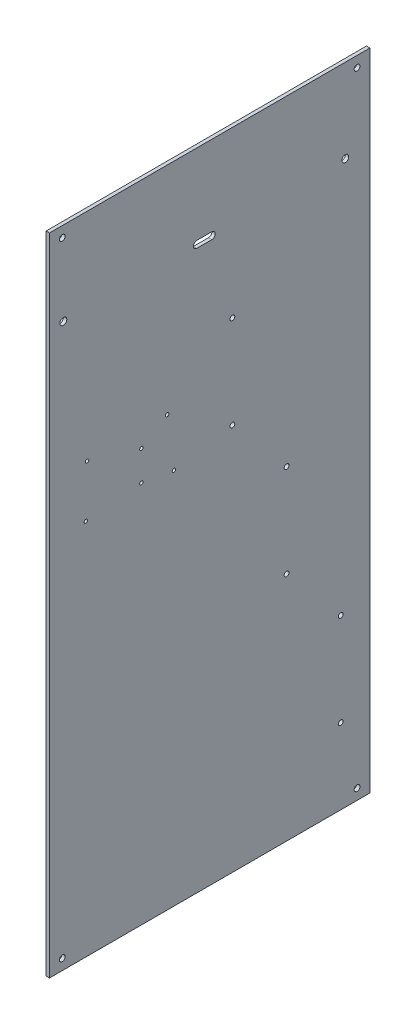
SolidWorks part; units mm, degrees
ref_plane "Front Plane" through (0, 0, 0) normal (0, 0, 1) x (1, 0, 0)
ref_plane "Top Plane" through (0, 0, 0) normal (0, 1, 0) x (1, 0, 0)
ref_plane "Right Plane" through (0, 0, 0) normal (1, 0, 0) x (0, 0, -1)
sketch "Sketch1" plane through (0, 0, 0) normal (1, 0, 0) x (0, 0, -1)
  line L1 (-150, -302.1) -> (150, -302.1)
  line L2 (-150, -302.1) -> (-150, 302.1)
  line L3 (-150, 302.1) -> (150, 302.1)
  line L4 (150, -302.1) -> (150, 302.1)
  line L5 (-150, -302.1) -> (150, 302.1) construction
  line L6 (-150, 302.1) -> (150, -302.1) construction
  point P0 (0, 0)
  dimension "D1" = 604.2
  dimension "D2" = 300
extrude "Boss-Extrude1" add sketch "Sketch1" along normal blind 1.5875 and the other way blind 1.5875
sketch "Sketch2" plane through (0, 0, 0) normal (1, 0, 0) x (0, 0, -1)
  line L0 (-150, 302.1) -> (-138, 302.1) construction
  line L1 (150, 302.1) -> (-150, 302.1) construction
  line L2 (-138, 302.1) -> (-138, 292.1) construction
  line L3 (0, 1.7463) -> (0, -1.7463) construction
  line L4 (1.7463, 0) -> (-1.7463, 0) construction
  circle A0 centre (-138, 292.1) radius 2.7
  circle A1 centre (138, 292.1) radius 2.7
  circle A2 centre (138, -292.1) radius 2.7
  circle A3 centre (-138, -292.1) radius 2.7
  dimension "D1" = 5.4
  dimension "D2" = 10
  dimension "D3" = 12
extrude "Cut-Extrude1" cut sketch "Sketch2" against normal through all both and the other way through all
sketch "Sketch3" plane through (0, 0, 0) normal (1, 0, 0) x (0, 0, -1)
  line L0 (-12, 223.8634) -> (2, 223.8634) construction
  line L1 (-12, 227.0634) -> (2, 227.0634)
  line L2 (-12, 220.6634) -> (2, 220.6634)
  circle A0 centre (-116.03, 51.3) radius 1.6
  circle A1 centre (-114.76, 99.56) radius 1.6
  circle A2 centre (-63.96, 56.38) radius 1.6
  circle A3 centre (-63.96, 84.32) radius 1.6
  circle A4 centre (-33.48, 51.3) radius 1.6
  circle A5 centre (-39.83, 99.56) radius 1.6
  circle A6 centre (21.25, 60.6) radius 2.25
  circle A7 centre (21.25, 147.6) radius 2.25
  circle A8 centre (72, 1.6) radius 2.25
  circle A9 centre (72, -85.4) radius 2.25
  circle A10 centre (122.75, -144.4) radius 2.25
  circle A11 centre (122.75, -231.4) radius 2.25
  circle A16 centre (-137, 223.8634) radius 3.2
  circle A17 centre (127, 223.8634) radius 3.2
  arc A18 (-12, 227.0634) -> (-12, 220.6634) centre (-12, 223.8634) ccw
  arc A19 (2, 220.6634) -> (2, 227.0634) centre (2, 223.8634) ccw
  point P45 (-5, 223.8634)
  dimension "D1" = 6.4
  dimension "D2" = 3.2
  dimension "D3" = 6.4
extrude "Cut-Extrude2" cut sketch "Sketch3" against normal through all both and the other way through all
